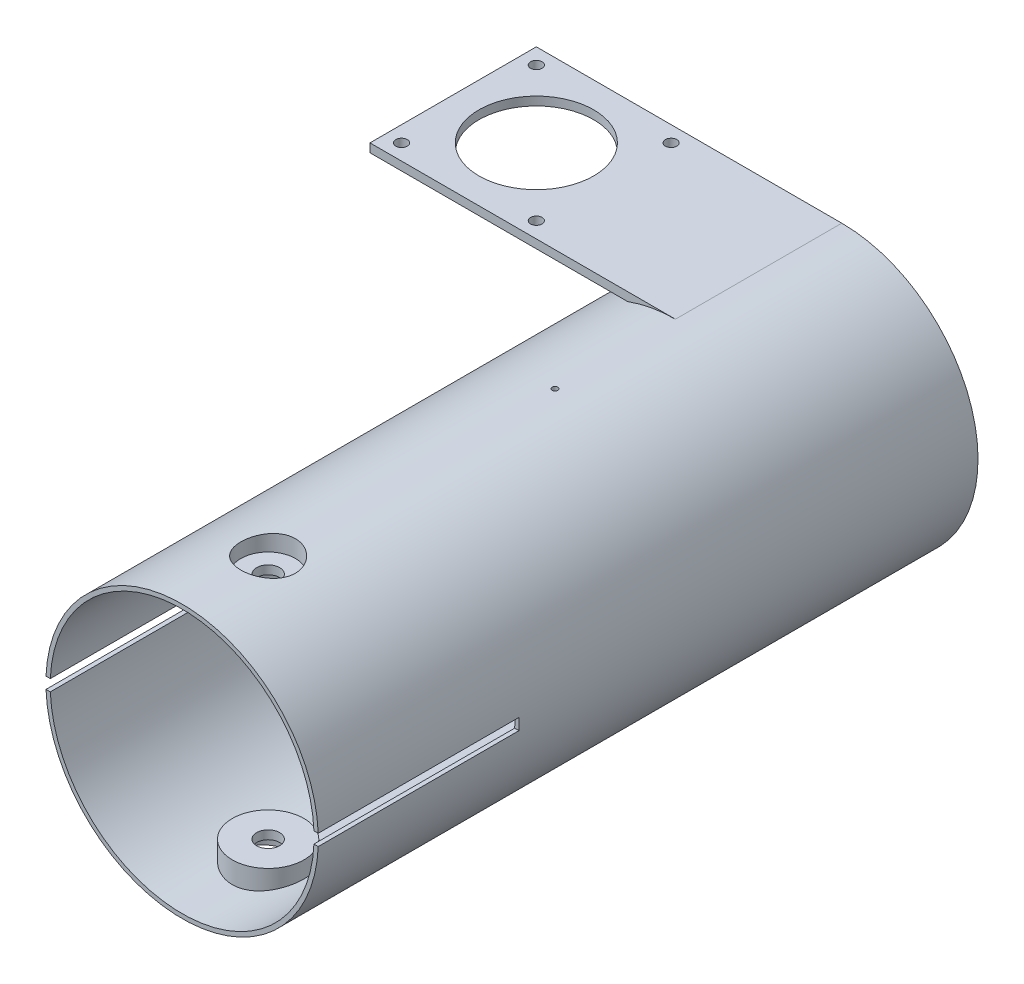
SolidWorks part; units mm, degrees
material "1060 Alloy"
ref_plane "Front Plane" through (0, 0, 0) normal (0, 0, 1) x (1, 0, 0)
ref_plane "Top Plane" through (0, 0, 0) normal (0, 1, 0) x (1, 0, 0)
ref_plane "Right Plane" through (0, 0, 0) normal (1, 0, 0) x (0, 0, -1)
other "Center of Mass"
sketch "Sketch1" plane through (0, 0, 0) normal (0, 0, 1) x (1, 0, 0)
  circle A0 centre (0, 0) radius 46
  circle A1 centre (0, 0) radius 47.5
  dimension "D1" = 92
  dimension "D2" = 95
extrude "Boss-Extrude1" add sketch "Sketch1" along normal blind 250
sketch "Sketch2" plane through (0, 0, 0) normal (0, 1, 0) x (1, 0, 0)
  line L0 (0, 0) -> (0, -120) construction
  circle A0 centre (0, -120) radius 1
  dimension "D2" = 2
  dimension "D1" = 120
extrude "Cut-Extrude1" cut sketch "Sketch2" against normal blind 250 and the other way blind 250
sketch "Sketch3" plane through (0, 0, 0) normal (0, 1, 0) x (1, 0, 0)
  line L0 (47.5, -250) -> (47.5, 0) construction
  line L1 (-47.5, 0) -> (47.5, 0)
  line L2 (-47.5, 0) -> (-47.5, -20)
  line L3 (-47.5, -20) -> (47.5, -20)
  line L4 (47.5, 0) -> (47.5, -20)
  dimension "D1" = 20
extrude "Cut-Extrude2" cut sketch "Sketch3" against normal blind 79 and the other way blind 75
sketch "Sketch4" plane through (0, 0, 0) normal (0, 1, 0) x (1, 0, 0)
  line L0 (0, 0) -> (0, -220) construction
  circle A0 centre (0, -220) radius 9.5
  dimension "D2" = 19
  dimension "D1" = 220
extrude "Cut-Extrude3" cut sketch "Sketch4" against normal blind 73 and the other way blind 64
ref_plane "Plane1" through (0, 41.5, 0) normal (0, 1, 0) x (1, 0, 0)
sketch "Sketch5" plane through (0, 41.5, 0) normal (0, 1, 0) x (1, 0, 0)
  circle A0 centre (0, -220) radius 9.5
  circle A1 centre (0, -220) radius 12.5
  dimension "D1" = 25
extrude "Boss-Extrude2" add sketch "Sketch5" along normal up to next
ref_plane "Plane2" through (0, -41.5, 0) normal (0, 1, 0) x (1, 0, 0)
sketch "Sketch10" plane through (0, 41.5, 0) normal (0, -1, 0) x (1, 0, 0)
  circle A0 centre (0, 220) radius 12.5
  circle A1 centre (0, 220) radius 4
  dimension "D1" = 8
extrude "Boss-Extrude7" add sketch "Sketch10" along normal blind 3
sketch "Sketch12" plane through (0, -41.5, 0) normal (0, 1, 0) x (1, 0, 0)
  line L0 (-47.5, -250) -> (47.5, -250) construction
  circle A0 centre (0, -220) radius 9.5
  circle A1 centre (0, -220) radius 12.5
  dimension "D1" = 25
  dimension "D2" = 30
extrude "Boss-Extrude8" add sketch "Sketch12" against normal up to next
sketch "Sketch13" plane through (0, -41.5, 0) normal (0, 1, 0) x (1, 0, 0)
  circle A0 centre (0, -220) radius 12.5
  circle A1 centre (0, -220) radius 4
  dimension "D1" = 8
extrude "Boss-Extrude9" add sketch "Sketch13" along normal blind 3
ref_plane "Plane3" through (0, 0, 20) normal (0, 0, 1) x (1, 0, 0)
sketch "Sketch17" plane through (0, 0, 20) normal (0, 0, 1) x (1, 0, 0)
  line L0 (0, 47.5) -> (-106.5, 47.5)
  line L1 (-106.5, 47.5) -> (-106.5, 44.5)
  line L2 (-106.5, 44.5) -> (-16.6132, 44.5)
  circle A0 centre (0, 0) radius 47.5 construction
  arc A2 (0, 47.5) -> (-16.6132, 44.5) centre (0, 0) ccw
  dimension "D1" = 106.5
  dimension "D2" = 3
extrude "Boss-Extrude11" add sketch "Sketch17" along normal blind 58
sketch "Sketch18" plane through (0, 47.5, 0) normal (0, 1, 0) x (1, 0, 0)
  line L0 (-106.5, -78) -> (-101, -78) construction
  line L1 (0, -78) -> (-106.5, -78) construction
  line L2 (-101, -78) -> (-101, -72.5) construction
  line L3 (-106.5, -49) -> (-77.5, -49) construction
  line L4 (-106.5, -78) -> (-106.5, -20) construction
  line L5 (-77.5, -49) -> (-77.5, -20) construction
  line L6 (-52.25, -20) -> (52.25, -20) construction
  circle A0 centre (-101, -72.5) radius 2
  circle A1 centre (-101, -25.5) radius 2
  circle A2 centre (-54, -25.5) radius 2
  circle A3 centre (-54, -72.5) radius 2
  circle A4 centre (-77.5, -49) radius 20
  dimension "D4" = 4
  dimension "D5" = 40
  dimension "D1" = 5.5
  dimension "D2" = 5.5
  dimension "D3" = 29
extrude "Cut-Extrude5" cut sketch "Sketch18" against normal blind 58
sketch "Sketch19" plane through (0, 0, 0) normal (1, 0, 0) x (0, 0, -1)
  line L0 (-250, 0) -> (-180, 0) construction
  line L1 (-250, 47.5) -> (-250, -47.5) construction
  line L2 (-180, 0) -> (-180, -2)
  line L3 (-180, -2) -> (-250, -2)
  line L4 (-250, -2) -> (-250, 0)
  line L5 (-250, 0) -> (-250, 2)
  line L6 (-250, 2) -> (-180, 2)
  line L7 (-180, 2) -> (-180, 0)
  dimension "D1" = 70
  dimension "D2" = 2
  dimension "D3" = 2
  dimension "D4" = 2
extrude "Cut-Extrude6" cut sketch "Sketch19" against normal blind 82 and the other way blind 98
